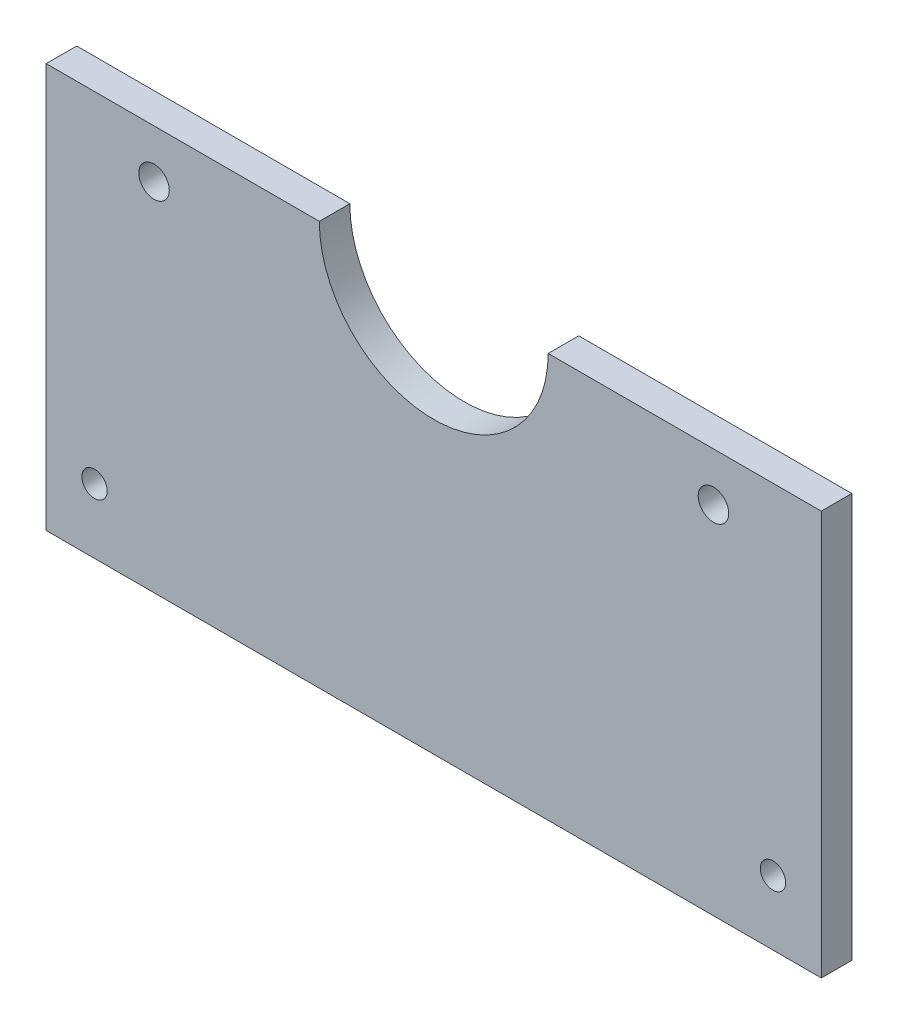
SolidWorks part; units mm, degrees
ref_plane "Front Plane" through (0, 0, 0) normal (0, 0, 1) x (1, 0, 0)
ref_plane "Top Plane" through (0, 0, 0) normal (0, 1, 0) x (1, 0, 0)
ref_plane "Right Plane" through (0, 0, 0) normal (1, 0, 0) x (0, 0, -1)
sketch "Sketch2" plane through (0, 0, 0) normal (0, 0, 1) x (1, 0, 0)
  line L0 (-55, 70) -> (55, 70) construction
  line L1 (-76.2, 0) -> (76.2, 0)
  line L2 (-76.2, 0) -> (-76.2, 79.5)
  line L3 (-76.2, 79.5) -> (76.2, 79.5) construction
  line L4 (76.2, 0) -> (76.2, 79.5)
  line L5 (0, 70) -> (0, 0) construction
  line L6 (0, 70) -> (0, 79.5) construction
  line L7 (0, 79.5) -> (-22.5, 79.5) construction
  line L8 (-22.5, 79.5) -> (-76.2, 79.5)
  line L9 (22.5, 79.5) -> (76.2, 79.5)
  circle A0 centre (-55, 70) radius 3
  circle A1 centre (55, 70) radius 3
  circle A2 centre (-55, 70) radius 16 construction
  circle A3 centre (55, 70) radius 16 construction
  arc A4 (-22.5, 79.5) -> (22.5, 79.5) centre (0, 79.5) ccw
  point P6 (0, 0)
  dimension "D1" = 6
  dimension "D2" = 32
  dimension "D5" = 45
  dimension "D3" = 110
  dimension "D4" = 9.5
  dimension "D6" = 152.4
  dimension "D7" = 70
extrude "Boss-Extrude1" add sketch "Sketch2" along normal mid plane 6
sketch "Sketch3" plane through (0, 0, 3) normal (0, 0, 1) x (1, 0, 0)
  line L1 (-76.2, 0) -> (-66.7, 0) construction
  line L2 (-76.2, 0) -> (-76.2, 12.7) construction
  line L3 (-76.2, 12.7) -> (-66.7, 12.7) construction
  line L4 (-66.7, 0) -> (-66.7, 12.7) construction
  line L5 (76.2, 0) -> (66.7, 0) construction
  line L6 (76.2, 0) -> (76.2, 12.7) construction
  line L7 (76.2, 12.7) -> (66.7, 12.7) construction
  line L8 (66.7, 0) -> (66.7, 12.7) construction
  circle A0 centre (-66.7, 12.7) radius 2.5
  circle A1 centre (66.7, 12.7) radius 2.5
  dimension "D1" = 12.7
  dimension "D2" = 5
  dimension "D3" = 9.5
extrude "Cut-Extrude1" cut sketch "Sketch3" against normal blind 6
